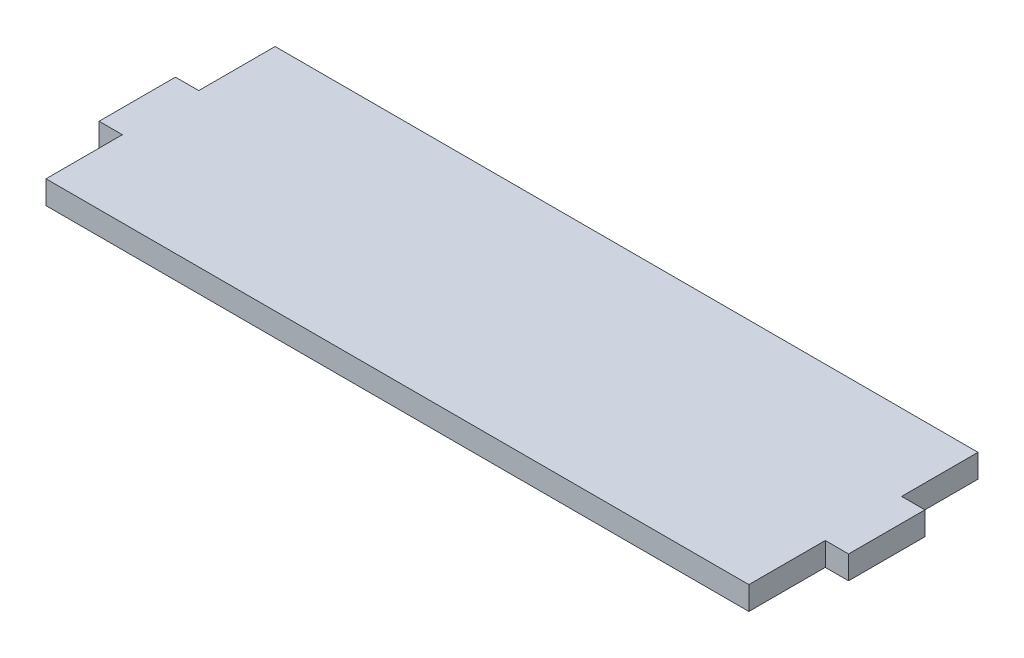
SolidWorks part; units mm, degrees
ref_plane "Front Plane" through (0, 0, 0) normal (0, 0, 1) x (1, 0, 0)
ref_plane "Top Plane" through (0, 0, 0) normal (0, 1, 0) x (1, 0, 0)
ref_plane "Right Plane" through (0, 0, 0) normal (1, 0, 0) x (0, 0, -1)
sketch "Sketch1" plane through (0, 0, 0) normal (0, 1, 0) x (1, 0, 0)
  line L1 (-96.5, 29.5) -> (96.5, 29.5)
  line L2 (-96.5, 29.5) -> (-96.5, -29.5)
  line L3 (-96.5, -29.5) -> (96.5, -29.5)
  line L4 (96.5, 29.5) -> (96.5, -29.5)
  line L5 (-96.5, 29.5) -> (96.5, -29.5) construction
  line L6 (-96.5, -29.5) -> (96.5, 29.5) construction
  line L7 (-96.5, 29.5) -> (-90.5, 29.5)
  line L8 (-96.5, 29.5) -> (-96.5, 9.8333)
  line L9 (-96.5, 9.8333) -> (-90.5, 9.8333)
  line L10 (-90.5, 29.5) -> (-90.5, 9.8333)
  line L11 (-90.5, 9.8333) -> (-96.5, 9.8333)
  line L12 (-90.5, 9.8333) -> (-90.5, -9.8333)
  line L13 (-90.5, -9.8333) -> (-96.5, -9.8333)
  line L14 (-96.5, 9.8333) -> (-96.5, -9.8333)
  line L15 (-96.5, -9.8333) -> (-90.5, -9.8333)
  line L16 (-96.5, -9.8333) -> (-96.5, -29.5)
  line L17 (-96.5, -29.5) -> (-90.5, -29.5)
  line L18 (-90.5, -9.8333) -> (-90.5, -29.5)
  point P0 (0, 0)
  dimension "D1" = 193
  dimension "D3" = 6
  dimension "D2" = 59
sketch "Sketch2" plane through (0, 0, 0) normal (0, 0, 1) x (1, 0, 0)
  line L0 (0, 0) -> (0, 6) construction
  line L1 (-96.5, 0) -> (96.5, 0) construction
  dimension "D1" = 6
extrude "Boss-Extrude1" add sketch "Sketch1" along normal up to vertex (6 mm away) contours L2 L3 L4 L1 up to point (0, 6, 0)
extrude "Cut-Extrude1" cut sketch "Sketch1<3>" along normal through all contours L18 L13 L2 L3 | L10 L1 L2 L9 region at (-93.5, 0, -19.6667) region at (-93.5, 0, 19.6667)
sketch "Sketch1<3>" plane through (0, 0, 0) normal (0, 1, 0) x (1, 0, 0) same geometry as "Sketch1"
mirror "Mirror1" about plane through (0, 0, 0) normal (1, 0, 0) of "Cut-Extrude1"
equation "\"glass_width\"= 181"
equation "\"glass_height\"= 151"
equation "\"glass_thickness\"= 2.5"
equation "\"brood_space\"= 42"
equation "\"t1\"= 6"
equation "\"t2\"= 6"
equation "\"box_depth\"= \"brood_space\" + \"glass_thickness\" + \"glass_thickness\" + \"t2\" + \"t2\""
equation "\"box_width\"= \"glass_width\" + \"t1\" + \"t1\""
equation "\"food_height\"= 70"
equation "\"box_height\"= \"glass_height\" + ( \"t1\" * 3 ) + \"food_height\""
equation "\"D1@Sketch2\"=\"t1\""
equation "\"D1@Sketch1\"=\"box_width\""
equation "\"D3@Sketch1\"=\"t1\""
equation "\"D2@Sketch1\"=\"box_depth\""
equation "\"entry_height\"= 24"
equation "\"entry_diameter\"= 8"
equation "\"food_top_clearance\"= 10"
equation "\"bar_width\"= 20"
equation "\"glassblocker_lower_height\"= 10"
equation "\"lower_edge_stickout\"=6"
